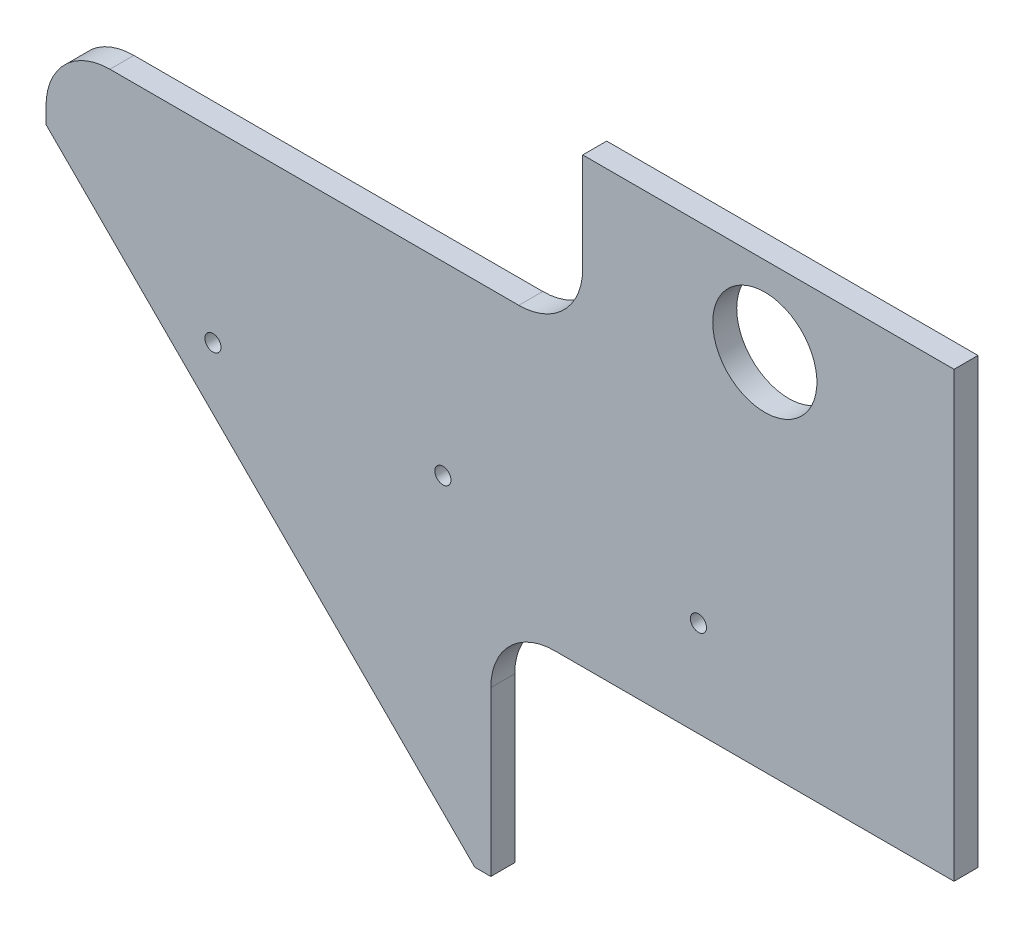
SolidWorks part; units mm, degrees
ref_plane "Front Plane" through (0, 0, 0) normal (0, 0, 1) x (1, 0, 0)
ref_plane "Top Plane" through (0, 0, 0) normal (0, 1, 0) x (1, 0, 0)
ref_plane "Right Plane" through (0, 0, 0) normal (1, 0, 0) x (0, 0, -1)
sketch "Sketch1" plane through (0, 0, 0) normal (0, 0, 1) x (1, 0, 0)
  line L0 (-138.2594, 48.9915) -> (32.2106, -121.4785)
  line L1 (32.2106, -121.4785) -> (222.7106, -121.4785)
  line L2 (-138.2594, 145.2215) -> (-138.2594, 48.9915)
  line L3 (-138.2594, 145.2215) -> (222.7106, 145.2215)
  line L4 (222.7106, -121.4785) -> (222.7106, 145.2215)
  circle A0 centre (147.4906, 113.4715) radius 20.701
  circle A2 centre (147.4906, 113.4715) radius 69.85 construction
  circle A3 centre (147.4906, 113.4715) radius 285.75 construction
  point P0 (0, 0)
  point P2 (147.4906, 113.4715)
  dimension "D4" = 234.95
  dimension "D1" = 45
  dimension "D2" = 266.7
  dimension "D5" = 247.65
extrude "Boss-Extrude1" add sketch "Sketch1" along normal blind 9.525
sketch "Sketch2" plane through (0, 0, 9.525) normal (0, 0, 1) x (1, 0, 0)
  line L0 (32.2106, -121.4785) -> (222.7106, -121.4785) construction
  line L1 (222.7106, -121.4785) -> (38.5606, -121.4785)
  line L2 (222.7106, -121.4785) -> (222.7106, -31.0571)
  line L3 (222.7106, -31.0571) -> (38.5606, -31.0571)
  line L4 (38.5606, -121.4785) -> (38.5606, -31.0571)
extrude "Cut-Extrude1" cut sketch "Sketch2" against normal through all contours L3 L4 L1 L2
fillet "Fillet1" radius 25.4 1 edges at (38.5606, -31.0571, 4.7625)
sketch "Sketch4" plane through (0, 0, 9.525) normal (0, 0, 1) x (1, 0, 0)
  line L1 (-138.2594, 145.2215) -> (-138.2594, 48.9915) construction
  line L3 (-138.2594, 145.2215) -> (75.1006, 145.2215)
  line L4 (-138.2594, 145.2215) -> (-138.2594, 80.7415)
  line L5 (-138.2594, 80.7415) -> (75.1006, 80.7415)
  line L6 (75.1006, 145.2215) -> (75.1006, 80.7415)
extrude "Cut-Extrude2" cut sketch "Sketch4" against normal through all contours L5 L6 L3 L4
fillet "Fillet2" radius 25.4 2 edges at (-138.2594, 80.7415, 4.7625) (75.1006, 80.7415, 4.7625)
hole_wizard "Ø6.4 (6.4) Diameter Hole2" positions "Sketch15" profile "Sketch14" hole size "Ø6.4" standard "Lanco STD" end condition through all
sketch "Sketch15" plane through (0, 0, 0) normal (0, 0, -1) x (-1, 0, 0)
  point P3 (-121.1106, 7.0429)
  point P6 (-19.5106, 7.0429)
  point P9 (71.8957, 7.0429)
sketch "Sketch14" plane through (121.1106, 7.0429, 0) normal (1, 0, 0) x (0, 1, 0)
  line L0 (0, 0) -> (0, 9.525)
  line L1 (0, 9.525) -> (3.2, 9.525)
  line L2 (3.2, 9.525) -> (3.2, 0)
  line L5 (3.2, 0) -> (0, 0)
  line L11 (0, -6.35) -> (0, 107.95) construction
  dimension "Thru Hole Dia." = 6.4
  dimension "Thru Hole Depth" = 9.525
